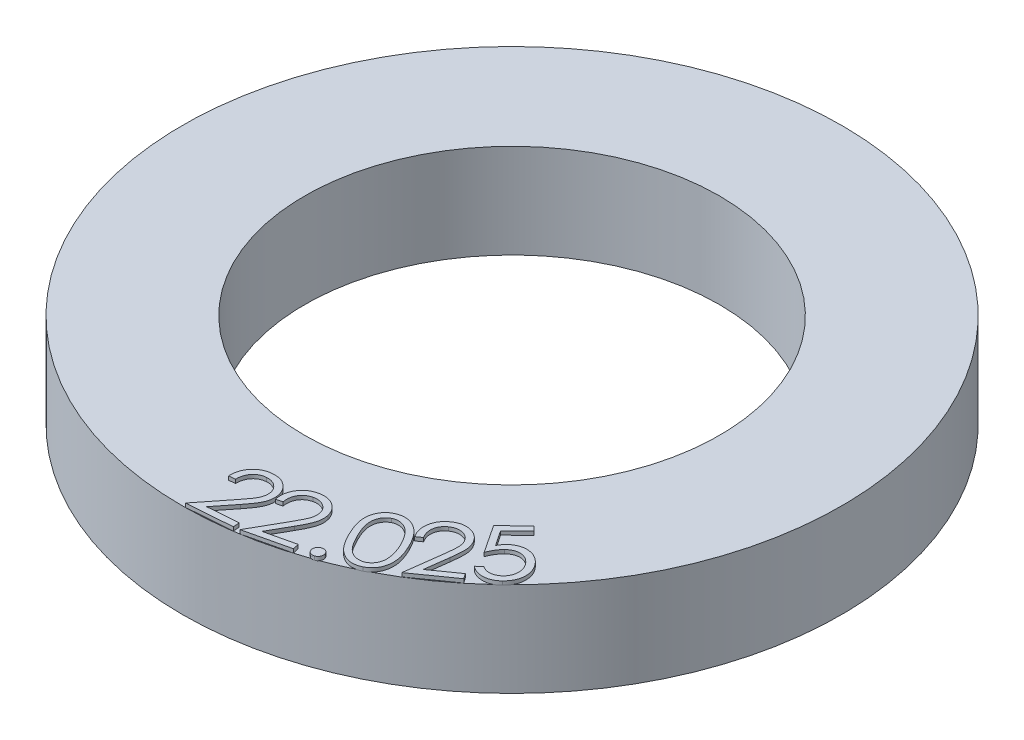
SolidWorks part; units mm, degrees
ref_plane "Front Plane" through (0, 0, 0) normal (0, 0, 1) x (1, 0, 0)
ref_plane "Top Plane" through (0, 0, 0) normal (0, 1, 0) x (1, 0, 0)
ref_plane "Right Plane" through (0, 0, 0) normal (1, 0, 0) x (0, 0, -1)
ref_axis "X" through (-88.99, 0, 0) along (1, 0, 0)
ref_axis "Y" through (0, 55, 0) along (0, -1, 0)
ref_axis "Z" through (0, 0, -88.99) along (0, 0, 1)
sketch "Sketch1" plane through (0, 0, 0) normal (0, 1, 0) x (1, 0, 0)
  circle A0 centre (0, 0) radius 17.5
  circle A1 centre (0, 0) radius 11.0125
  dimension "D1" = 35
  dimension "D2" = 22.025
extrude "Boss-Extrude1" add sketch "Sketch1" along normal blind 5
sketch "Sketch2" plane through (0, 5, 0) normal (0, 1, 0) x (1, 0, 0)
  text T0 "22.025"
extrude "Boss-Extrude2" add sketch "Sketch2" along normal blind 0.2
